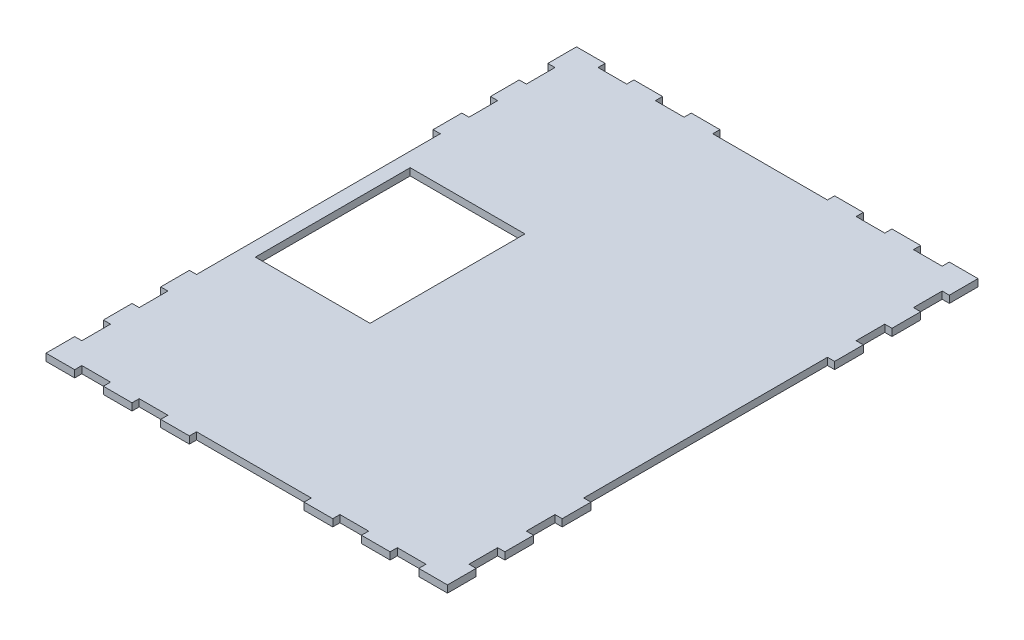
SolidWorks part; units mm, degrees
material "Acrylic (Medium-high impact)"
ref_plane "Front Plane" through (0, 0, 0) normal (0, 0, 1) x (1, 0, 0)
ref_plane "Top Plane" through (0, 0, 0) normal (0, 1, 0) x (1, 0, 0)
ref_plane "Right Plane" through (0, 0, 0) normal (1, 0, 0) x (0, 0, -1)
sketch "Sketch1" plane through (0, 0, 0) normal (0, 1, 0) x (1, 0, 0)
  line L0 (0, 209.55) -> (0, 196.85)
  line L1 (0, 0) -> (177.8, 0)
  line L2 (0, 0) -> (0, 234.95)
  line L3 (0, 234.95) -> (177.8, 234.95)
  line L4 (177.8, 0) -> (177.8, 234.95)
  line L5 (0, 234.95) -> (3.175, 234.95)
  line L6 (0, 234.95) -> (0, 0)
  line L7 (0, 0) -> (3.175, 0)
  line L8 (3.175, 234.95) -> (3.175, 0)
  line L9 (177.8, 234.95) -> (174.625, 234.95)
  line L10 (177.8, 234.95) -> (177.8, 0)
  line L11 (177.8, 0) -> (174.625, 0)
  line L12 (174.625, 234.95) -> (174.625, 0)
  line L13 (0, 234.95) -> (3.175, 234.95)
  line L14 (0, 234.95) -> (0, 222.25)
  line L15 (0, 222.25) -> (3.175, 222.25)
  line L16 (3.175, 234.95) -> (3.175, 222.25)
  line L17 (0, 209.55) -> (3.175, 209.55)
  line L18 (3.175, 209.55) -> (3.175, 196.85)
  line L19 (0, 196.85) -> (3.175, 196.85)
  line L20 (0, 184.15) -> (0, 171.45)
  line L21 (0, 184.15) -> (3.175, 184.15)
  line L22 (3.175, 184.15) -> (3.175, 171.45)
  line L23 (0, 171.45) -> (3.175, 171.45)
  line L24 (0, 117.475) -> (177.8, 117.475) construction
  line L25 (88.9, 234.95) -> (88.9, 0) construction
  line L26 (177.8, 171.45) -> (174.625, 171.45)
  line L27 (174.625, 184.15) -> (174.625, 171.45)
  line L28 (177.8, 184.15) -> (174.625, 184.15)
  line L29 (177.8, 184.15) -> (177.8, 171.45)
  line L30 (177.8, 196.85) -> (174.625, 196.85)
  line L31 (174.625, 209.55) -> (174.625, 196.85)
  line L32 (177.8, 209.55) -> (174.625, 209.55)
  line L33 (174.625, 234.95) -> (174.625, 222.25)
  line L34 (177.8, 222.25) -> (174.625, 222.25)
  line L35 (177.8, 234.95) -> (177.8, 222.25)
  line L36 (177.8, 234.95) -> (174.625, 234.95)
  line L37 (177.8, 234.95) -> (177.8, 0)
  line L38 (177.8, 234.95) -> (174.625, 234.95)
  line L39 (177.8, 209.55) -> (177.8, 196.85)
  line L40 (177.8, 25.4) -> (177.8, 38.1)
  line L41 (177.8, 0) -> (174.625, 0)
  line L42 (177.8, 0) -> (174.625, 0)
  line L43 (177.8, 0) -> (177.8, 12.7)
  line L44 (177.8, 12.7) -> (174.625, 12.7)
  line L45 (174.625, 0) -> (174.625, 12.7)
  line L46 (177.8, 25.4) -> (174.625, 25.4)
  line L47 (174.625, 25.4) -> (174.625, 38.1)
  line L48 (177.8, 38.1) -> (174.625, 38.1)
  line L49 (177.8, 50.8) -> (177.8, 63.5)
  line L50 (177.8, 50.8) -> (174.625, 50.8)
  line L51 (174.625, 50.8) -> (174.625, 63.5)
  line L52 (177.8, 63.5) -> (174.625, 63.5)
  line L53 (0, 63.5) -> (3.175, 63.5)
  line L54 (3.175, 50.8) -> (3.175, 63.5)
  line L55 (0, 50.8) -> (3.175, 50.8)
  line L56 (0, 50.8) -> (0, 63.5)
  line L57 (0, 38.1) -> (3.175, 38.1)
  line L58 (3.175, 25.4) -> (3.175, 38.1)
  line L59 (0, 25.4) -> (3.175, 25.4)
  line L60 (3.175, 0) -> (3.175, 12.7)
  line L61 (0, 12.7) -> (3.175, 12.7)
  line L62 (0, 0) -> (0, 12.7)
  line L63 (0, 0) -> (3.175, 0)
  line L64 (177.8, 0) -> (174.625, 0)
  line L65 (0, 0) -> (3.175, 0)
  line L66 (0, 0) -> (177.8, 0)
  line L67 (0, 25.4) -> (0, 38.1)
  dimension "D1" = 234.95
  dimension "D2" = 177.8
  dimension "D3" = 3.175
  dimension "D4" = 3.175
  dimension "D5" = 12.7
  dimension "D6" = 3.175
  dimension "D7" = 3
extrude "Boss-Extrude1" add sketch "Sketch1" along normal blind 3.175 contours L6 L55 L8 L53 | L6 L59 L8 L57 | L61 L2 L1 L8 | L6 L23 L8 L21 | L0 L19 L8 L17 | L6 L15 L8 L3 | L4 L44 L12 L1 | L37 L48 L12 L46 | L37 L52 L12 L50 | L34 L10 L3 L12 | L10 L32 L12 L30 | L10 L28 L12 L26 | L52 L12 L26 L27 L28 L30 L31 L32 L34 L33 L3 L8 L1 L45 L44 L46 L47 L48 L50 L51 region at (1.5875, 0, -203.2) region at (1.5875, 0, -228.6) region at (88.9, 0, -117.475) region at (1.5875, 0, -177.8) region at (1.5875, 0, -57.15) region at (176.2125, 0, -228.6) region at (1.5875, 0, -31.75) region at (176.2125, 0, -203.2) region at (1.5875, 0, -6.35) region at (176.2125, 0, -177.8) region at (176.2125, 0, -57.15) region at (176.2125, 0, -6.35) region at (176.2125, 0, -31.75)
sketch "Sketch5" plane through (0, 3.175, 0) normal (0, 1, 0) x (1, 0, 0)
  line L0 (88.9, 0) -> (88.9, 18.3402) construction
  line L1 (0, 0) -> (177.8, 0) construction
  line L3 (0, 0) -> (12.7, 0)
  line L4 (0, 0) -> (0, 3.175)
  line L5 (0, 3.175) -> (12.7, 3.175)
  line L6 (12.7, 0) -> (12.7, 3.175)
  line L10 (25.4, 3.175) -> (38.1, 3.175)
  line L11 (25.4, 0) -> (38.1, 0)
  line L12 (38.1, 0) -> (38.1, 3.175)
  line L13 (25.4, 0) -> (25.4, 3.175)
  line L14 (50.8, 3.175) -> (63.5, 3.175)
  line L15 (50.8, 0) -> (63.5, 0)
  line L16 (63.5, 0) -> (63.5, 3.175)
  line L17 (50.8, 0) -> (50.8, 3.175)
  line L18 (0, 3.175) -> (177.8, 3.175)
  line L19 (127, 0) -> (127, 3.175)
  line L20 (114.3, 0) -> (114.3, 3.175)
  line L21 (127, 0) -> (114.3, 0)
  line L22 (127, 3.175) -> (114.3, 3.175)
  line L23 (152.4, 0) -> (152.4, 3.175)
  line L24 (139.7, 0) -> (139.7, 3.175)
  line L25 (152.4, 0) -> (139.7, 0)
  line L26 (152.4, 3.175) -> (139.7, 3.175)
  line L27 (165.1, 0) -> (165.1, 3.175)
  line L28 (177.8, 3.175) -> (165.1, 3.175)
  line L29 (177.8, 0) -> (177.8, 3.175)
  line L30 (177.8, 0) -> (165.1, 0)
  line L63 (0, 63.5) -> (0, 50.8)
  line L64 (0, 50.8) -> (3.175, 50.8)
  line L65 (3.175, 50.8) -> (3.175, 38.1)
  line L66 (3.175, 38.1) -> (0, 38.1)
  line L67 (0, 38.1) -> (0, 25.4)
  line L68 (0, 25.4) -> (3.175, 25.4)
  line L69 (3.175, 25.4) -> (3.175, 12.7)
  line L70 (3.175, 12.7) -> (0, 12.7)
  line L71 (0, 12.7) -> (0, 0)
  line L72 (0, 0) -> (177.8, 0)
  line L73 (177.8, 0) -> (177.8, 12.7)
  line L74 (177.8, 12.7) -> (174.625, 12.7)
  line L75 (174.625, 12.7) -> (174.625, 25.4)
  line L76 (174.625, 25.4) -> (177.8, 25.4)
  line L77 (177.8, 25.4) -> (177.8, 38.1)
  line L78 (177.8, 38.1) -> (174.625, 38.1)
  line L79 (174.625, 38.1) -> (174.625, 50.8)
  line L80 (174.625, 50.8) -> (177.8, 50.8)
  line L81 (177.8, 50.8) -> (177.8, 63.5)
  line L82 (177.8, 63.5) -> (174.625, 63.5)
  line L83 (174.625, 63.5) -> (174.625, 171.45)
  line L84 (174.625, 171.45) -> (177.8, 171.45)
  line L85 (177.8, 171.45) -> (177.8, 184.15)
  line L86 (177.8, 184.15) -> (174.625, 184.15)
  line L87 (174.625, 184.15) -> (174.625, 196.85)
  line L88 (174.625, 196.85) -> (177.8, 196.85)
  line L89 (177.8, 196.85) -> (177.8, 209.55)
  line L90 (177.8, 209.55) -> (174.625, 209.55)
  line L91 (174.625, 209.55) -> (174.625, 222.25)
  line L92 (174.625, 222.25) -> (177.8, 222.25)
  line L93 (177.8, 222.25) -> (177.8, 234.95)
  line L94 (177.8, 234.95) -> (0, 234.95)
  line L95 (0, 234.95) -> (0, 222.25)
  line L96 (0, 222.25) -> (3.175, 222.25)
  line L97 (3.175, 222.25) -> (3.175, 209.55)
  line L98 (3.175, 209.55) -> (0, 209.55)
  line L99 (0, 209.55) -> (0, 196.85)
  line L100 (0, 196.85) -> (3.175, 196.85)
  line L101 (3.175, 196.85) -> (3.175, 184.15)
  line L102 (3.175, 184.15) -> (0, 184.15)
  line L103 (0, 184.15) -> (0, 171.45)
  line L104 (0, 171.45) -> (3.175, 171.45)
  line L105 (3.175, 171.45) -> (3.175, 63.5)
  line L106 (3.175, 63.5) -> (0, 63.5)
  line L107 (0, 63.5) -> (0, 50.8)
  line L108 (0, 50.8) -> (3.175, 50.8)
  line L109 (3.175, 50.8) -> (3.175, 38.1)
  line L110 (3.175, 38.1) -> (0, 38.1)
  line L111 (0, 38.1) -> (0, 25.4)
  line L112 (0, 25.4) -> (3.175, 25.4)
  line L113 (3.175, 25.4) -> (3.175, 12.7)
  line L114 (3.175, 12.7) -> (0, 12.7)
  line L115 (0, 12.7) -> (0, 0)
  line L116 (0, 0) -> (177.8, 0)
  line L117 (177.8, 0) -> (177.8, 12.7)
  line L118 (177.8, 12.7) -> (174.625, 12.7)
  line L119 (174.625, 12.7) -> (174.625, 25.4)
  line L120 (174.625, 25.4) -> (177.8, 25.4)
  line L121 (177.8, 25.4) -> (177.8, 38.1)
  line L122 (177.8, 38.1) -> (174.625, 38.1)
  line L123 (174.625, 38.1) -> (174.625, 50.8)
  line L124 (174.625, 50.8) -> (177.8, 50.8)
  line L125 (177.8, 50.8) -> (177.8, 63.5)
  line L126 (177.8, 63.5) -> (174.625, 63.5)
  line L127 (174.625, 63.5) -> (174.625, 171.45)
  line L128 (174.625, 171.45) -> (177.8, 171.45)
  line L129 (177.8, 171.45) -> (177.8, 184.15)
  line L130 (177.8, 184.15) -> (174.625, 184.15)
  line L131 (174.625, 184.15) -> (174.625, 196.85)
  line L132 (174.625, 196.85) -> (177.8, 196.85)
  line L133 (177.8, 196.85) -> (177.8, 209.55)
  line L134 (177.8, 209.55) -> (174.625, 209.55)
  line L135 (174.625, 209.55) -> (174.625, 222.25)
  line L136 (174.625, 222.25) -> (177.8, 222.25)
  line L137 (177.8, 222.25) -> (177.8, 234.95)
  line L138 (177.8, 234.95) -> (0, 234.95)
  line L139 (0, 234.95) -> (0, 222.25)
  line L140 (0, 222.25) -> (3.175, 222.25)
  line L141 (3.175, 222.25) -> (3.175, 209.55)
  line L142 (3.175, 209.55) -> (0, 209.55)
  line L143 (0, 209.55) -> (0, 196.85)
  line L144 (0, 196.85) -> (3.175, 196.85)
  line L145 (3.175, 196.85) -> (3.175, 184.15)
  line L146 (3.175, 184.15) -> (0, 184.15)
  line L147 (0, 184.15) -> (0, 171.45)
  line L148 (0, 171.45) -> (3.175, 171.45)
  line L149 (3.175, 171.45) -> (3.175, 63.5)
  line L150 (3.175, 63.5) -> (0, 63.5)
  point P22 (88.9, 3.175)
  dimension "D1" = 3.175
  dimension "D2" = 12.7
  dimension "D4" = 0
  dimension "D3" = 3
extrude "Cut-Extrude4" cut sketch "Sketch5" against normal blind 7.62 contours L6 L116 L13 L18 | L12 L116 L17 L18 | L116 L0 L18 L16 | L0 L116 L20 L18 | L19 L116 L24 L18 | L23 L116 L27 L18 region at (76.2, 3.175, -1.5875) region at (101.6, 3.175, -1.5875) region at (44.45, 3.175, -1.5875) region at (133.35, 3.175, -1.5875) region at (19.05, 3.175, -1.5875) region at (158.75, 3.175, -1.5875)
ref_plane "Plane2" through (0, 0, -117.475) normal (0, 0, 1) x (1, 0, 0)
mirror "Mirror1" about plane through (0, 0, -117.475) normal (0, 0, 1) of "Cut-Extrude4"
sketch "Sketch7" plane through (0, 3.175, 0) normal (0, 1, 0) x (1, 0, 0)
  line L0 (3.175, 117.475) -> (174.625, 117.475) construction
  line L1 (3.175, 171.45) -> (3.175, 63.5) construction
  line L2 (174.625, 171.45) -> (174.625, 63.5) construction
  line L3 (3.175, 117.475) -> (9.525, 117.475) construction
  line L4 (9.525, 117.475) -> (9.525, 151.765)
  line L6 (9.525, 151.765) -> (60.325, 151.765)
  line L7 (9.525, 151.765) -> (9.525, 83.185)
  line L8 (9.525, 83.185) -> (60.325, 83.185)
  line L9 (60.325, 151.765) -> (60.325, 83.185)
  dimension "D1" = 6.35
  dimension "D2" = 34.29
  dimension "D3" = 68.58
  dimension "D4" = 50.8
extrude "Cut-Extrude5" cut sketch "Sketch7" against normal blind 7.62 contours L6 L9 L8 L7
